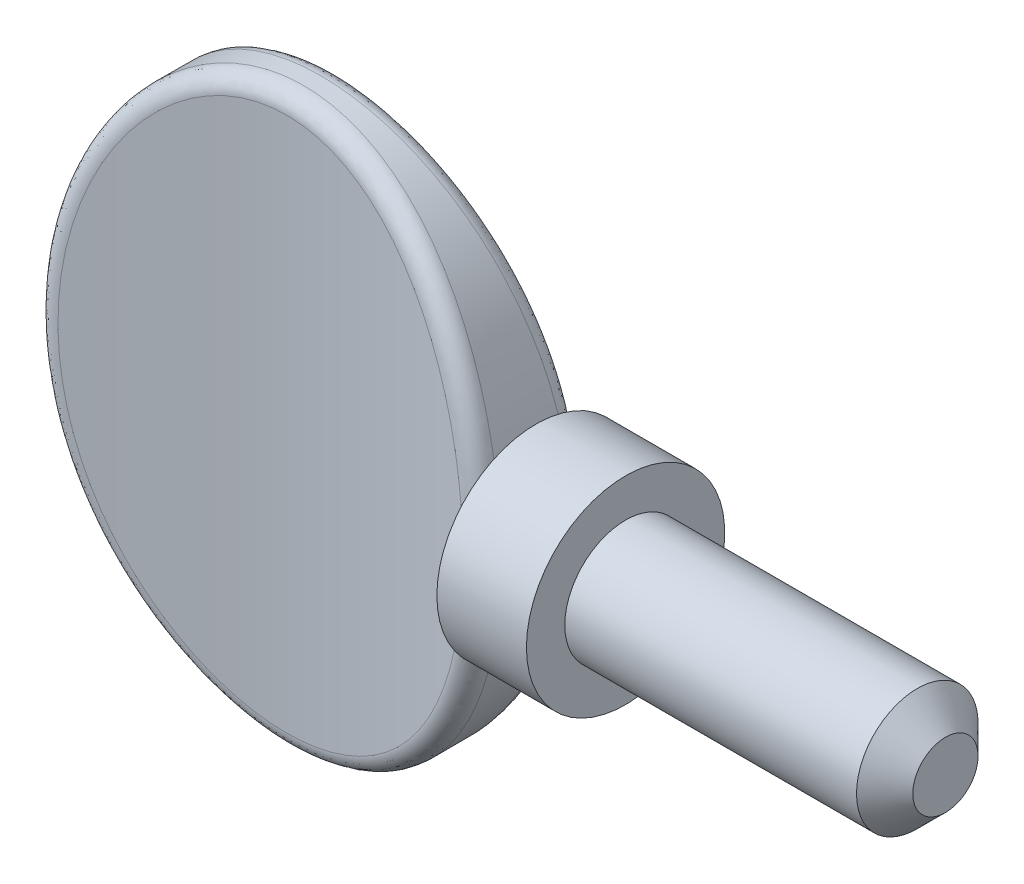
SolidWorks part; units mm, degrees
ref_plane "Front" through (0, 0, 0) normal (0, 0, 1) x (1, 0, 0)
ref_plane "Top" through (0, 0, 0) normal (0, 1, 0) x (1, 0, 0)
ref_plane "Right" through (0, 0, 0) normal (1, 0, 0) x (0, 0, -1)
ref_axis "Axis1" through (-50, 0, 0) along (1, 0, 0)
sketch "Sketch1" plane through (0, 0, 0) normal (0, 0, 1) x (1, 0, 0)
  line L0 (0, 0) -> (25.146, 0) construction
  line L1 (12.446, -3.937) -> (12.446, 3.937)
  ellipse E0 centre (0, 0) end of major axis (0, 11.303) minor radius 8.89
  dimension "D2" = 3.556
extrude "Extrude1" add sketch "Sketch1" along normal mid plane 4.572
sketch "Sketch2" plane through (0, 0, 0) normal (0, 1, 0) x (1, 0, 0)
  line L0 (8.89, 2.286) -> (-8.89, 2.286) construction
  line L1 (0, 0) -> (0, 1.1721) construction
  line L2 (-1.7991, 0) -> (2.0444, 0) construction
  line L3 (-8.89, -2.286) -> (8.89, -2.286) construction
  line L6 (-8.89, 2.286) -> (-8.89, -2.286)
  line L7 (8.89, 2.286) -> (8.89, -2.286)
  arc A0 (-8.89, 2.286) -> (8.89, 2.286) centre (0, 32.766) ccw
  arc A1 (-8.89, -2.286) -> (8.89, -2.286) centre (0, -32.766) cw
extrude "Cut-Extrude1" cut sketch "Sketch2" against normal through all and the other way through all flip side to cut
fillet "Fillet3" radius 0.6773 2 edges at (-8.875, -0.6558, 2.2816) (-1.5369, -11.1328, -1.0532)
sketch "Sketch3" plane through (0, 0, 0) normal (0, 1, 0) x (1, 0, 0)
  line L0 (12.446, 3.937) -> (12.446, 2.413)
  line L1 (0, 0) -> (21.0288, 0) construction
  line L2 (0, 0) -> (25.146, 0) construction
  line L3 (12.446, 2.413) -> (12.446, 0) construction
  line L4 (12.446, 2.413) -> (24.0284, 2.413)
  line L5 (25.146, 0) -> (25.146, 1.2954)
  line L6 (12.446, 3.937) -> (8.89, 3.937)
  line L7 (7.2364, 1.8517) -> (7.2364, 0)
  line L8 (8.89, 0) -> (8.89, 3.937) construction
  line L9 (7.2364, 0) -> (25.146, 0)
  line L10 (25.146, 1.2954) -> (24.0284, 2.413)
  arc A0 (8.89, 3.937) -> (7.2364, 1.8517) centre (6.7483, 3.937) cw
  arc A3 (-8.89, 2.286) -> (8.89, 2.286) centre (0, 32.766) ccw construction
  dimension "D1" = 7.874
  dimension "D2" = 45
revolve "Revolve1" add sketch "Sketch3" angle 360 about L0
cosmetic thread "Cosmetic Thread1" [suppressed]
sketch "Sketch4" plane through (0, 0, 0) normal (0, 0, 1) x (1, 0, 0)
  line L0 (0, 0) -> (27.7993, 0) construction
  line L1 (23.6295, 2.413) -> (24.0284, 1.7221)
  line L2 (24.0284, 1.7221) -> (24.4273, 2.413)
  line L3 (24.4273, 2.413) -> (24.4273, 3.2108)
  line L4 (24.4273, 3.2108) -> (23.6295, 3.2108)
  line L5 (23.6295, 3.2108) -> (23.6295, 2.413)
  line L6 (24.0284, 2.413) -> (24.0284, -2.413) construction
  dimension "D1" = 3.4442
  dimension "D2" = 4.826
revolve "Cut-Revolve10" [suppressed] cut sketch "Sketch4" angle 360 about L0
pattern_linear "LPattern10" [suppressed] count 11 along (-1, 0, 0) of bodies 109
equation "\"D2@Sketch1\" = \"B@Sketch1\" / 6"
equation "\"D1@Sketch3\" = \"E@Sketch1\""
equation "\"D1@Fillet3\" = \"C1@Sketch2\" / 3"
equation "\"D1@Sketch4\" = \"D2@Cosmetic Thread1\""
equation "\"D2@Sketch4\" = \"DIA@Sketch3\""
equation "\"D1@LPattern10\" = (  \"L@Sketch1\"  -  ( \"DIA@Sketch3\" - \"flat_dia@Sketch3\" )  / 2 ) / \"P@LPattern10\" "
